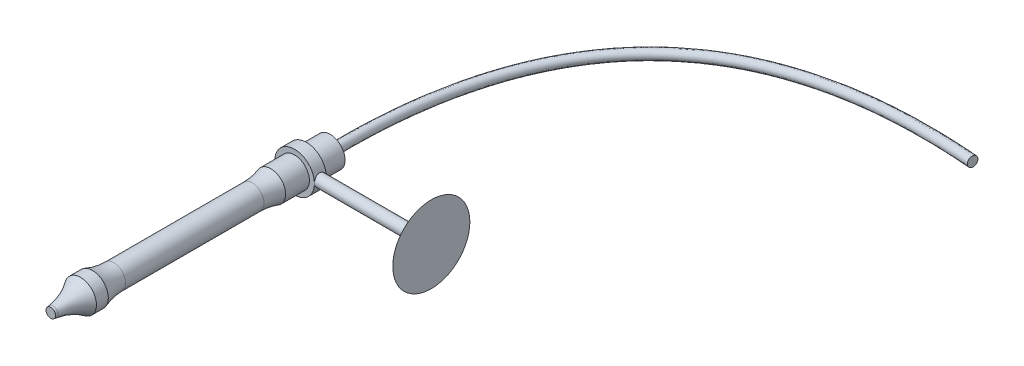
SolidWorks part; units mm, degrees
ref_plane "Front Plane" through (0, 0, 0) normal (0, 0, 1) x (1, 0, 0)
ref_plane "Top Plane" through (0, 0, 0) normal (0, 1, 0) x (1, 0, 0)
ref_plane "Right Plane" through (0, 0, 0) normal (1, 0, 0) x (0, 0, -1)
sketch "Sketch1" plane through (0, 0, 0) normal (0, 0, 1) x (1, 0, 0)
  circle A0 centre (0, 0) radius 2.5
  dimension "D1" = 5
extrude "Boss-Extrude1" add sketch "Sketch1" along normal blind 10
sketch "Sketch2" plane through (0, 0, 10) normal (0, 0, 1) x (1, 0, 0)
  circle A0 centre (0, 0) radius 2
  dimension "D1" = 4
extrude "Boss-Extrude2" add sketch "Sketch2" along normal blind 30
sketch "Sketch3" plane through (0, 0, 40) normal (0, 0, 1) x (1, 0, 0)
  circle A0 centre (0, 0) radius 2.6727
extrude "Boss-Extrude3" add sketch "Sketch3" along normal blind 2
sketch "Sketch4" plane through (0, 0, 42) normal (0, 0, 1) x (1, 0, 0)
  circle A0 centre (0, 0) radius 1.424
extrude "Boss-Extrude4" add sketch "Sketch4" along normal blind 5 draft 7
fillet "Fillet1" radius 10 1 edges at (2, 0, 10)
fillet "Fillet2" radius 10 2 edges at (1.424, 0, 42) (2, 0, 40)
ref_plane "Plane1" through (0, 0, 5) normal (0, 0, -1) x (-1, 0, 0)
sketch "Sketch5" plane through (0, 0, 5) normal (0, 0, -1) x (-1, 0, 0)
  circle A0 centre (0, 0) radius 3.3355
extrude "Boss-Extrude5" add sketch "Sketch5" along normal mid plane 2
sketch "Sketch6" plane through (0, 0, 0) normal (1, 0, 0) x (0, 0, -1)
  line L0 (-5, -2.75) -> (-5, 2.75) construction
  circle A0 centre (-5, 0) radius 0.9876
extrude "Boss-Extrude6" add sketch "Sketch6" along normal blind 20
sketch "Sketch7" plane through (20, 0, 0) normal (1, 0, 0) x (0, 0, -1)
  circle A1 centre (-5, 0) radius 0.9876
  circle A2 centre (-5, 0) radius 0.9876
  dimension "D1" = 0
extrude "Boss-Extrude7" add sketch "Sketch7" along normal blind 2 draft 70 draft outward yes
sketch "Sketch8" plane through (0, 0, 0) normal (0, 0, -1) x (-1, 0, 0)
  circle A0 centre (0, 0) radius 0.8231
sketch "Sketch9" plane through (0, 0, 0) normal (0, 1, 0) x (1, 0, 0)
  spline S0 degree 2 poles (0, 0) (-1.0934, 57.227) (55.4731, 52.5786) knots 0 0 0 1 1 1
sweep "Sweep2" add profiles "Sketch8" path "Sketch9"
